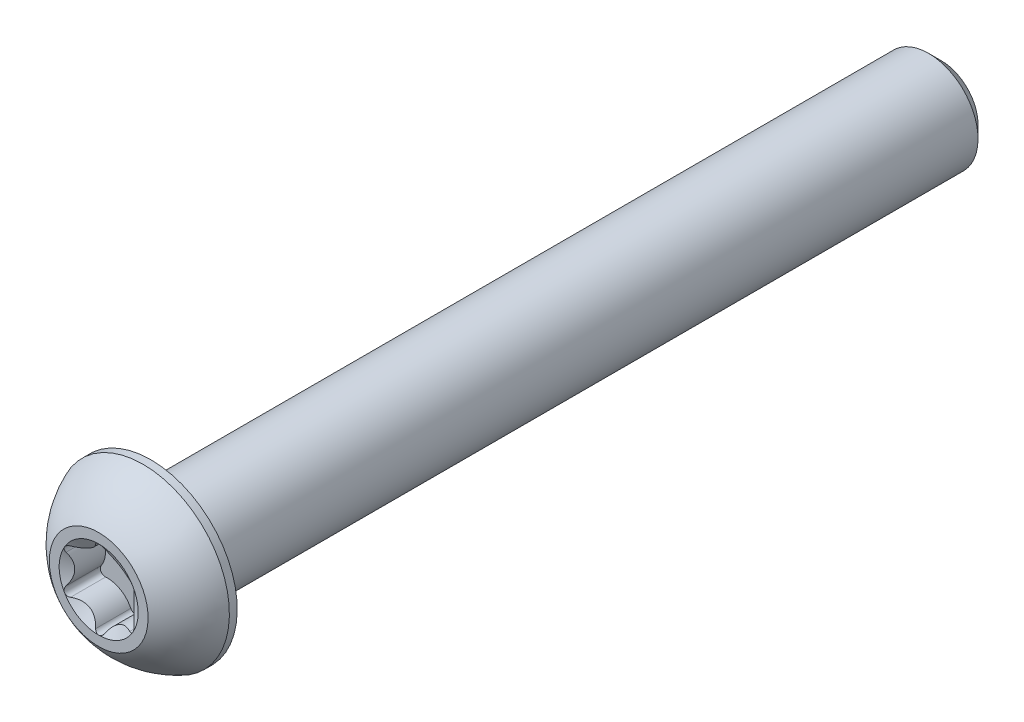
SolidWorks part; units mm, degrees
ref_plane "Front Plane" through (0, 0, 0) normal (0, 0, 1) x (1, 0, 0)
ref_plane "Top Plane" through (0, 0, 0) normal (0, 1, 0) x (1, 0, 0)
ref_plane "Right Plane" through (0, 0, 0) normal (1, 0, 0) x (0, 0, -1)
sketch "Sketch1" plane through (0, 0, 0) normal (1, 0, 0) x (0, 0, -1)
  line L0 (0, 0) -> (0, 3.175) construction
  line L1 (2.8499, 5.5499) -> (3.3528, 5.5499) construction
  line L2 (3.3528, 5.5499) -> (3.3528, 3.175) construction
  line L3 (3.3528, 3.175) -> (54.1528, 3.175) construction
  line L4 (54.1528, 3.175) -> (54.1528, 0) construction
  line L5 (54.1528, 0) -> (0, 0) construction
  line L6 (54.0734, 3.3125) -> (55.3434, 3.3125) construction
  line L7 (55.3434, 3.3125) -> (54.7084, 2.2126) construction
  line L8 (54.7084, 2.2126) -> (54.0734, 3.3125) construction
  line L9 (54.6291, 2.3501) -> (54.7878, 2.3501) construction
  line L10 (54.7084, 2.3501) -> (54.7084, 2.2126) construction
  line L11 (54.1131, 3.2437) -> (55.3037, 3.2437) construction
  line L12 (54.1528, 3.175) -> (55.2641, 3.175) construction
  line L13 (54.7084, 3.175) -> (54.7084, 3.3125) construction
  line L14 (54.1528, 2.36) -> (54.1528, 3.3125) construction
  line L15 (54.1528, 3.3125) -> (53.2003, 3.3125) construction
  line L16 (53.2003, 3.3125) -> (54.1528, 2.36) construction
  arc A0 (0, 3.175) -> (2.8499, 5.5499) centre (5.0603, 0) cw construction
  point P7 (2.8499, -5.5499)
  point P10 (3.3528, 5.5499)
  point P11 (0, 3.175)
  point P12 (54.1528, -3.175)
  point P13 (2.8499, 5.5499)
  point P16 (54.1528, 3.175)
  point P25 (54.7084, 3.175)
  point P28 (54.7084, 3.2437)
  point P30 (54.6291, 2.3501)
  point P31 (54.7878, 2.3501)
  point P32 (54.1528, 3.175)
  point P33 (55.2641, 3.175)
  point P34 (55.3434, 3.3125)
  point P35 (54.0734, 3.3125)
  point P36 (52.2478, -3.175)
  dimension "Head Dia" = 11.0998
  dimension "Head Height" = 3.3528
  dimension "D1" = 0.5029
  dimension "Thread OD" = 6.35
  dimension "Pitch" = 1.27
  dimension "D2" = 0.1588
  dimension "D3" = 45
  dimension "D4" = 0.9525
  dimension "D5" = 1.905
  dimension "Length" = 50.8
sketch "Sketch2" plane through (0, 0, 0) normal (0, 0, 1) x (1, 0, 0)
  line L0 (0, 1.905) -> (0, 2.2225) construction
  line L1 (0, 2.2225) -> (0, 2.54) construction
  line L2 (0, 0) -> (-2.1997, 1.27) construction
  line L3 (0, 0) -> (-2.54, 0) construction
  line L4 (0, 0) -> (-2.1997, -1.27) construction
  circle A0 centre (0, 0) radius 2.54 construction
  circle A1 centre (0, 0) radius 2.2225 construction
  circle A2 centre (0, 0) radius 1.905 construction
  circle A3 centre (0, 0) radius 5.5499 construction
  arc A4 (-2.1997, 1.27) -> (-2.1887, 0.9348) centre (-1.9247, 1.1113) ccw construction
  arc A5 (-2.1887, 0.9348) -> (-2.1887, -0.9348) centre (-3.587, 0) cw construction
  arc A6 (-2.1997, -1.27) -> (-2.1887, -0.9348) centre (-1.9247, -1.1113) cw construction
  point P7 (-2.54, 0)
  point P9 (-2.2225, 0)
  point P10 (-1.905, 0)
  point P11 (1.905, 0)
  point P12 (2.2225, 0)
  point P13 (2.54, 0)
  point P15 (-5.5499, 0)
  point P16 (5.5499, 0)
  point P20 (-2.1997, 1.27)
  point P21 (-2.1997, -1.27)
  point P26 (0, -2.54)
  dimension "D1" = 11.0998
  dimension "D2" = 5.08
  dimension "D3" = 3.81
  dimension "D4" = 30
sketch "Sketch3" plane through (0, 0, 0) normal (1, 0, 0) x (0, 0, -1)
  line L0 (2.8499, 5.5499) -> (3.3528, 5.5499) construction
  line L1 (3.3528, 5.5499) -> (3.3528, 3.175) construction
  line L2 (3.3528, 3.175) -> (54.1528, 3.175) construction
  line L3 (2.8499, 5.5499) -> (3.3528, 5.5499)
  line L4 (3.3528, 5.5499) -> (3.3528, 3.175)
  line L5 (3.3528, 3.175) -> (53.3378, 3.175)
  line L6 (53.2003, 3.3125) -> (54.1528, 2.36) construction
  line L7 (53.3378, 3.175) -> (54.1528, 2.36)
  line L8 (54.1528, 3.175) -> (54.1528, 0) construction
  line L9 (54.1528, 2.36) -> (54.1528, 0)
  line L10 (0, 0) -> (0, 3.175) construction
  line L11 (0, 0) -> (0, 3.175)
  line L12 (54.1528, 0) -> (0, 0) construction
  line L13 (54.1528, 0) -> (0, 0)
  arc A0 (2.8499, 5.5499) -> (0, 3.175) centre (5.0603, 0) ccw construction
  arc A1 (2.8499, 5.5499) -> (0, 3.175) centre (5.0603, 0) ccw
revolve "Revolve1" add sketch "Sketch3" angle 360 about L13
sketch "Sketch4" plane through (0, 0, 0) normal (0, 0, 1) x (1, 0, 0)
  line L0 (0, 0) -> (-2.1997, -1.27) construction
  line L1 (0, 0) -> (-2.1997, 1.27) construction
  line L2 (0, 0) -> (-2.1997, -1.27)
  line L3 (0, 0) -> (-2.1997, 1.27)
  arc A0 (-2.1887, -0.9348) -> (-2.1997, -1.27) centre (-1.9247, -1.1113) ccw construction
  arc A1 (-2.1887, -0.9348) -> (-2.1887, 0.9348) centre (-3.587, 0) ccw construction
  arc A2 (-2.1997, 1.27) -> (-2.1887, 0.9348) centre (-1.9247, 1.1113) ccw construction
  arc A3 (-2.1887, -0.9348) -> (-2.1997, -1.27) centre (-1.9247, -1.1113) ccw
  arc A4 (-2.1887, -0.9348) -> (-2.1887, 0.9348) centre (-3.587, 0) ccw
  arc A5 (-2.1997, 1.27) -> (-2.1887, 0.9348) centre (-1.9247, 1.1113) ccw
extrude "Cut-Extrude1" cut sketch "Sketch4" against normal blind 2.347
pattern_circular "CirPattern1" count 6 over 360 about axis through (0, 0, -54.1528) along (0, 0, 1) of "Cut-Extrude1" reverse direction yes
sketch "Sketch5" plane through (0, 0, 0) normal (0, 0, 1) x (1, 0, 0)
  circle A0 centre (0, 0) radius 2.54 construction
  circle A1 centre (0, 0) radius 2.54
extrude "Cut-Extrude2" cut sketch "Sketch5" against normal blind 2.347 draft 60
ref_axis "Center Axis 1" through (0, 0, -54.1528) along (0, 0, 1)
sketch "Sketch6" [suppressed] plane through (0, 0, -54.1528) normal (0, 0, -1) x (-1, 0, 0)
  circle A0 centre (0, 0) radius 3.175
curve "Helix/Spiral1" [suppressed] pitch 1.27 height 52.07 turns 41
split "Split1" [suppressed] bodies to split 107
sketch "Sketch7" [suppressed] plane through (0, 0, 0) normal (1, 0, 0) x (0, 0, -1)
  line L0 (54.6291, 2.3501) -> (54.7878, 2.3501) construction
  line L1 (54.1131, 3.2437) -> (55.3037, 3.2437) construction
  line L2 (54.6291, 2.3501) -> (54.7878, 2.3501)
  line L3 (54.1131, 3.2437) -> (55.3037, 3.2437)
  line L4 (54.1131, 3.2437) -> (54.6291, 2.3501)
  line L5 (54.7878, 2.3501) -> (55.3037, 3.2437)
sweep "Cut-Sweep1" [suppressed] cut profiles "Sketch7" path "Helix/Spiral1"
combine bodies "Combine1" [suppressed] operation type add bodies to combine 110 109
equation "\"D1@Sketch1\"=\"Head Height@Sketch1\"*.15"
equation "\"D2@Sketch1\"=\"Pitch@Sketch1\"/8"
equation "\"D4@Sketch1\"=\"Pitch@Sketch1\"*.75"
equation "\"D1@Sketch2\"=\"Head Dia@Sketch1\""
equation "\"D2@Sketch2\"=\"Thread OD@Sketch1\"*.8"
equation "\"D3@Sketch2\"=(\"Thread OD@Sketch1\"*.8)*.75"
equation "\"D5@Sketch1\"=\"Pitch@Sketch1\"*1.5"
equation "\"D1@Cut-Extrude1\"=\"Head Height@Sketch1\"*.7"
equation "\"D1@Cut-Extrude2\"=\"Head Height@Sketch1\"*.7"
equation "\"D3@Helix/Spiral1\" = \"Length@Sketch1\" + \"Pitch@Sketch1\""
equation "\"D4@Helix/Spiral1\"=\"Pitch@Sketch1\""
